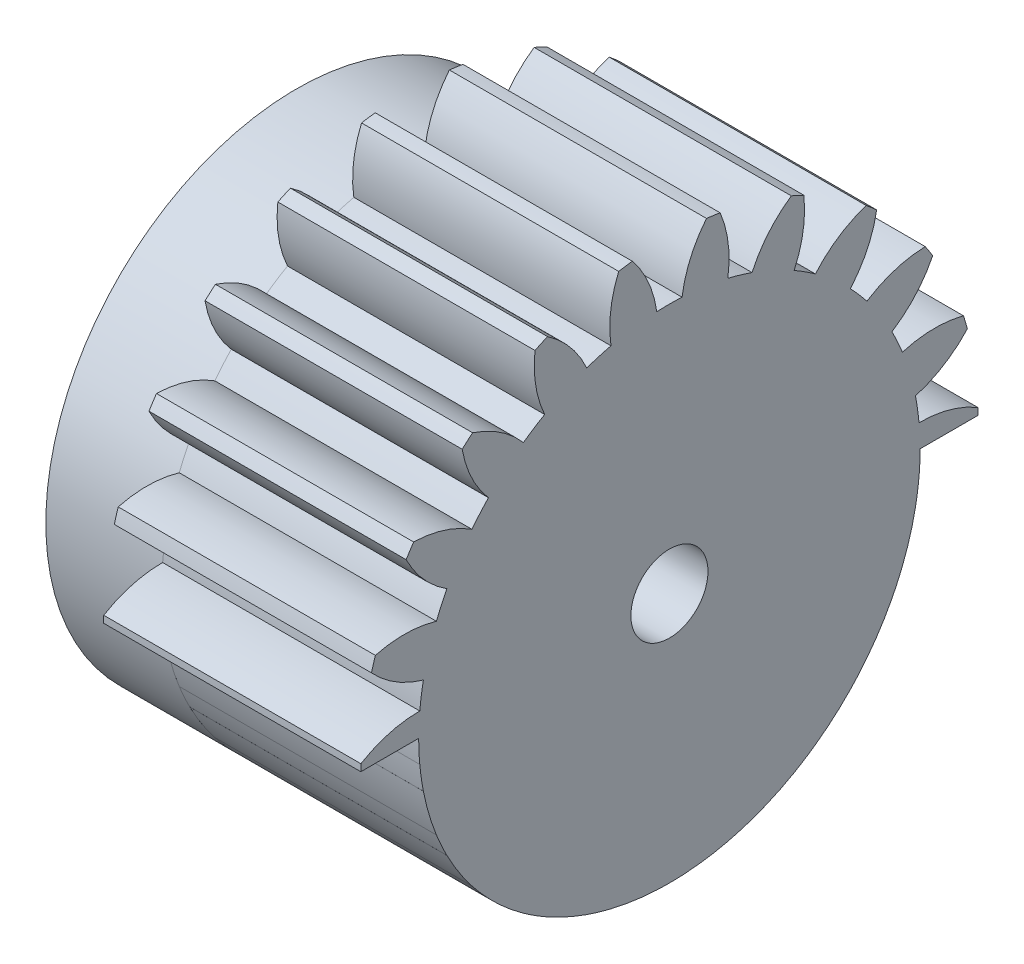
SolidWorks part; units mm, degrees
ref_plane "Front Plane" through (0, 0, 0) normal (0, 0, 1) x (1, 0, 0)
ref_plane "Top Plane" through (0, 0, 0) normal (0, 1, 0) x (1, 0, 0)
ref_plane "Right Plane" through (0, 0, 0) normal (1, 0, 0) x (0, 0, -1)
ref_plane "Plane2" through (4.0389, 0, 0) normal (1, 0, 0) x (0, 0, -1)
sketch "Sketch5" plane through (4.0389, 0, 0) normal (1, 0, 0) x (0, 0, -1)
  circle A0 centre (3.23, 4.4522) radius 1.5
  arc A1 (-8.767, 4.1839) -> (-6.4774, 3.5525) centre (-6.496, 7.9525) ccw
  arc A2 (-6.4774, 3.5525) -> (-6.3377, 2.5805) centre (3.23, 4.4522) ccw
  arc A3 (-6.3377, 2.5805) -> (-8.3567, 1.3296) centre (-5.1159, -1.6464) ccw
  arc A4 (-8.3567, 1.3296) -> (-8.2055, 0.8148) centre (3.23, 4.4522) ccw
  arc A5 (-8.2055, 0.8148) -> (-5.8308, 0.8541) centre (-7.0882, 5.0706) ccw
  arc A6 (-5.8308, 0.8541) -> (-5.4228, -0.0392) centre (3.23, 4.4522) ccw
  arc A7 (-5.4228, -0.0392) -> (-7.0076, -1.8082) centre (-3.0596, -3.7507) ccw
  arc A8 (-7.0076, -1.8082) -> (-6.7175, -2.2596) centre (3.23, 4.4522) ccw
  arc A9 (-6.7175, -2.2596) -> (-4.45, -1.5529) centre (-6.8444, 2.1386) ccw
  arc A10 (-4.45, -1.5529) -> (-3.807, -2.295) centre (3.23, 4.4522) ccw
  arc A11 (-3.807, -2.295) -> (-4.8292, -4.4389) centre (-0.4938, -5.1904) ccw
  arc A12 (-4.8292, -4.4389) -> (-4.4237, -4.7902) centre (3.23, 4.4522) ccw
  arc A13 (-4.4237, -4.7902) -> (-2.4471, -3.4733) centre (-5.7845, -0.606) ccw
  arc A14 (-2.4471, -3.4733) -> (-1.621, -4.0043) centre (3.23, 4.4522) ccw
  arc A15 (-1.621, -4.0043) -> (-1.9978, -6.3492) centre (2.3736, -5.8489) ccw
  arc A16 (-1.9978, -6.3492) -> (-1.5097, -6.5721) centre (3.23, 4.4522) ccw
  arc A17 (-1.5097, -6.5721) -> (0.0157, -4.7517) centre (-3.9943, -2.9408) ccw
  arc A18 (0.0157, -4.7517) -> (0.9579, -5.0284) centre (3.23, 4.4522) ccw
  arc A19 (0.9579, -5.0284) -> (1.257, -7.3845) centre (5.3105, -5.6729) ccw
  arc A20 (1.257, -7.3845) -> (1.7882, -7.4609) centre (3.23, 4.4522) ccw
  arc A21 (1.7882, -7.4609) -> (2.739, -5.2845) centre (-1.6189, -4.6766) ccw
  arc A22 (2.739, -5.2845) -> (3.721, -5.2845) centre (3.23, 4.4522) ccw
  arc A23 (3.721, -5.2845) -> (4.6718, -7.4609) centre (8.0788, -4.6766) ccw
  arc A24 (4.6718, -7.4609) -> (5.2029, -7.3845) centre (3.23, 4.4522) ccw
  arc A25 (5.2029, -7.3845) -> (5.502, -5.0284) centre (1.1494, -5.6729) ccw
  arc A26 (5.502, -5.0284) -> (6.4442, -4.7517) centre (3.23, 4.4522) ccw
  arc A27 (6.4442, -4.7517) -> (7.9696, -6.5721) centre (10.4542, -2.9408) ccw
  arc A28 (7.9696, -6.5721) -> (8.4577, -6.3492) centre (3.23, 4.4522) ccw
  arc A29 (8.4577, -6.3492) -> (8.0809, -4.0043) centre (4.0863, -5.8489) ccw
  arc A30 (8.0809, -4.0043) -> (8.907, -3.4733) centre (3.23, 4.4522) ccw
  arc A31 (8.907, -3.4733) -> (10.8836, -4.7902) centre (12.2444, -0.606) ccw
  arc A32 (10.8836, -4.7902) -> (11.2891, -4.4389) centre (3.23, 4.4522) ccw
  arc A33 (11.2891, -4.4389) -> (10.2669, -2.295) centre (6.9537, -5.1904) ccw
  arc A34 (10.2669, -2.295) -> (10.9099, -1.5529) centre (3.23, 4.4522) ccw
  arc A35 (10.9099, -1.5529) -> (13.1774, -2.2596) centre (13.3043, 2.1386) ccw
  arc A36 (13.1774, -2.2596) -> (13.4675, -1.8082) centre (3.23, 4.4522) ccw
  arc A37 (13.4675, -1.8082) -> (11.8827, -0.0392) centre (9.5195, -3.7507) ccw
  arc A38 (11.8827, -0.0392) -> (12.2907, 0.8541) centre (3.23, 4.4522) ccw
  arc A39 (12.2907, 0.8541) -> (14.6654, 0.8148) centre (13.5481, 5.0706) ccw
  arc A40 (14.6654, 0.8148) -> (14.8166, 1.3296) centre (3.23, 4.4522) ccw
  arc A41 (14.8166, 1.3296) -> (12.7976, 2.5805) centre (11.5758, -1.6464) ccw
  arc A42 (12.7976, 2.5805) -> (12.9374, 3.5525) centre (3.23, 4.4522) ccw
  arc A43 (12.9374, 3.5525) -> (15.227, 4.1839) centre (12.9559, 7.9525) ccw
  arc A44 (15.227, 4.1839) -> (15.227, 4.7205) centre (3.23, 4.4522) ccw
  arc A45 (15.227, 4.7205) -> (12.9374, 5.3518) centre (12.9559, 0.9519) ccw
  arc A46 (12.9374, 5.3518) -> (12.7976, 6.3238) centre (3.23, 4.4522) ccw
  arc A47 (12.7976, 6.3238) -> (14.8166, 7.5747) centre (11.5758, 10.5508) ccw
  arc A48 (14.8166, 7.5747) -> (14.6654, 8.0895) centre (3.23, 4.4522) ccw
  arc A49 (14.6654, 8.0895) -> (12.2907, 8.0503) centre (13.5481, 3.8338) ccw
  arc A50 (12.2907, 8.0503) -> (11.8827, 8.9435) centre (3.23, 4.4522) ccw
  arc A51 (11.8827, 8.9435) -> (13.4675, 10.7125) centre (9.5195, 12.655) ccw
  arc A52 (13.4675, 10.7125) -> (13.1774, 11.1639) centre (3.23, 4.4522) ccw
  arc A53 (13.1774, 11.1639) -> (10.9099, 10.4572) centre (13.3043, 6.7658) ccw
  arc A54 (10.9099, 10.4572) -> (10.2669, 11.1994) centre (3.23, 4.4522) ccw
  arc A55 (10.2669, 11.1994) -> (11.2891, 13.3432) centre (6.9537, 14.0947) ccw
  arc A56 (11.2891, 13.3432) -> (10.8836, 13.6946) centre (3.23, 4.4522) ccw
  arc A57 (10.8836, 13.6946) -> (8.907, 12.3777) centre (12.2444, 9.5103) ccw
  arc A58 (8.907, 12.3777) -> (8.0809, 12.9086) centre (3.23, 4.4522) ccw
  arc A59 (8.0809, 12.9086) -> (8.4577, 15.2536) centre (4.0863, 14.7533) ccw
  arc A60 (8.4577, 15.2536) -> (7.9696, 15.4765) centre (3.23, 4.4522) ccw
  arc A61 (7.9696, 15.4765) -> (6.4442, 13.6561) centre (10.4542, 11.8451) ccw
  arc A62 (6.4442, 13.6561) -> (5.502, 13.9327) centre (3.23, 4.4522) ccw
  arc A63 (5.502, 13.9327) -> (5.2029, 16.2889) centre (1.1494, 14.5772) ccw
  arc A64 (5.2029, 16.2889) -> (4.6718, 16.3652) centre (3.23, 4.4522) ccw
  arc A65 (4.6718, 16.3652) -> (3.721, 14.1888) centre (8.0788, 13.581) ccw
  arc A66 (3.721, 14.1888) -> (2.739, 14.1888) centre (3.23, 4.4522) ccw
  arc A67 (2.739, 14.1888) -> (1.7882, 16.3652) centre (-1.6189, 13.581) ccw
  arc A68 (1.7882, 16.3652) -> (1.257, 16.2889) centre (3.23, 4.4522) ccw
  arc A69 (1.257, 16.2889) -> (0.9579, 13.9327) centre (5.3105, 14.5772) ccw
  arc A70 (0.9579, 13.9327) -> (0.0157, 13.6561) centre (3.23, 4.4522) ccw
  arc A71 (0.0157, 13.6561) -> (-1.5097, 15.4765) centre (-3.9943, 11.8451) ccw
  arc A72 (-1.5097, 15.4765) -> (-1.9978, 15.2536) centre (3.23, 4.4522) ccw
  arc A73 (-1.9978, 15.2536) -> (-1.621, 12.9086) centre (2.3736, 14.7533) ccw
  arc A74 (-1.621, 12.9086) -> (-2.4471, 12.3777) centre (3.23, 4.4522) ccw
  arc A75 (-2.4471, 12.3777) -> (-4.4237, 13.6946) centre (-5.7845, 9.5103) ccw
  arc A76 (-4.4237, 13.6946) -> (-4.8292, 13.3432) centre (3.23, 4.4522) ccw
  arc A77 (-4.8292, 13.3432) -> (-3.807, 11.1994) centre (-0.4938, 14.0947) ccw
  arc A78 (-3.807, 11.1994) -> (-4.45, 10.4572) centre (3.23, 4.4522) ccw
  arc A79 (-4.45, 10.4572) -> (-6.7175, 11.1639) centre (-6.8444, 6.7658) ccw
  arc A80 (-6.7175, 11.1639) -> (-7.0076, 10.7125) centre (3.23, 4.4522) ccw
  arc A81 (-7.0076, 10.7125) -> (-5.4228, 8.9435) centre (-3.0596, 12.655) ccw
  arc A82 (-5.4228, 8.9435) -> (-5.8308, 8.0503) centre (3.23, 4.4522) ccw
  arc A83 (-5.8308, 8.0503) -> (-8.2055, 8.0895) centre (-7.0882, 3.8338) ccw
  arc A84 (-8.2055, 8.0895) -> (-8.3567, 7.5747) centre (3.23, 4.4522) ccw
  arc A85 (-8.3567, 7.5747) -> (-6.3377, 6.3238) centre (-5.1159, 10.5508) ccw
  arc A86 (-6.3377, 6.3238) -> (-6.4774, 5.3518) centre (3.23, 4.4522) ccw
  arc A87 (-6.4774, 5.3518) -> (-8.767, 4.7205) centre (-6.496, 0.9519) ccw
  arc A88 (-8.767, 4.7205) -> (-8.767, 4.1839) centre (3.23, 4.4522) ccw
extrude "Boss-Extrude1" add sketch "Sketch5" against normal blind 10 separate body
ref_plane "Plane3" through (0, 0, -3.23) normal (0, 0, 1) x (1, 0, 0)
sketch "Sketch10" plane through (0, 0, -3.23) normal (0, 0, 1) x (1, 0, 0)
  line L0 (-5.9611, 7.9022) -> (-5.9611, 14.2022)
  line L1 (-5.9611, 14.2022) -> (-10.4611, 14.2022)
  line L2 (-10.4611, 14.2022) -> (-10.4611, 7.9022)
  line L3 (-10.4611, 7.9022) -> (-5.9611, 7.9022)
  line L4 (-10.4611, 4.4522) -> (-5.9611, 4.4522) construction
revolve "Revolve2" add sketch "Sketch10" angle 360 about L4 reverse direction yes
sketch "Sketch11" plane through (4.0389, 0, 0) normal (1, 0, 0) x (0, 0, -1)
  line L1 (-9.27, 4.4522) -> (-6.52, 4.4522)
  line L2 (12.98, 4.4522) -> (15.73, 4.4522)
  arc A0 (-6.52, 4.4522) -> (12.98, 4.4522) centre (3.23, 4.4522) ccw
  arc A1 (-9.27, 4.4522) -> (15.73, 4.4522) centre (3.23, 4.4522) ccw
  dimension "D1" = 19.5
  dimension "D2" = 25
extrude "Cut-Extrude1" cut sketch "Sketch11" against normal blind 10
